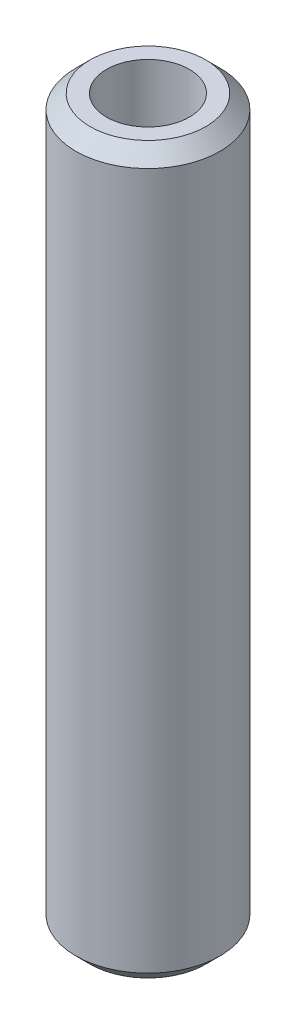
SolidWorks part; units mm, degrees
ref_plane "Front Plane" through (0, 0, 0) normal (0, 0, 1) x (1, 0, 0)
ref_plane "Top Plane" through (0, 0, 0) normal (0, 1, 0) x (1, 0, 0)
ref_plane "Right Plane" through (0, 0, 0) normal (1, 0, 0) x (0, 0, -1)
sketch "Sketch1" plane through (0, 0, 0) normal (0, 1, 0) x (1, 0, 0)
  circle A0 centre (0, 0) radius 22.5
  dimension "SHAFT_OD" = 45
extrude "Boss-Extrude1" add sketch "Sketch1" along normal blind 226.3095
sketch "Sketch2" plane through (0, 0, 0) normal (0, 1, 0) x (1, 0, 0)
  circle A0 centre (0, 0) radius 12.9211
  dimension "BORE_D" = 25.8422
extrude "Cut-Extrude1" cut sketch "Sketch2" along normal through all
chamfer "Chamfer1" distance 4.4489 angle 45 2 edges at (0, 226.3095, 22.5) (0, 0, 22.5)
